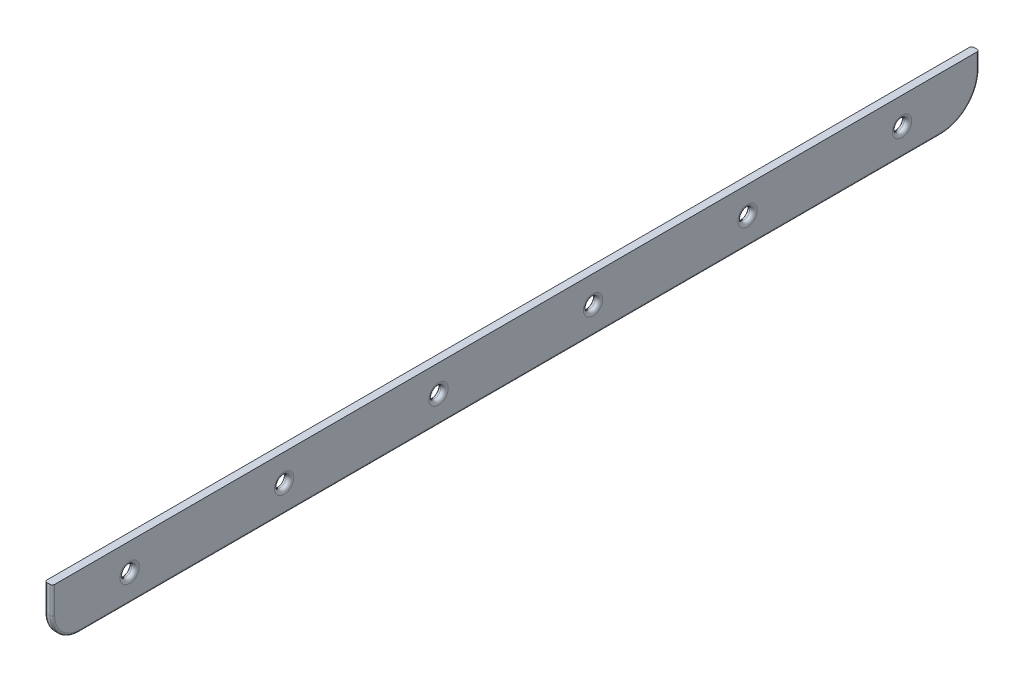
SolidWorks part; units mm, degrees
material "1.0037 (S235JR)"
ref_plane "Front Plane" through (0, 0, 0) normal (0, 0, 1) x (1, 0, 0)
ref_plane "Top Plane" through (0, 0, 0) normal (0, 1, 0) x (1, 0, 0)
ref_plane "Right Plane" through (0, 0, 0) normal (1, 0, 0) x (0, 0, -1)
sketch "Sketch1" plane through (0, 0, 0) normal (1, 0, 0) x (0, 0, -1)
  line L0 (-600, 0) -> (-600, -35)
  line L1 (-565, -70) -> (550, -70)
  line L3 (600, 0) -> (-600, 0)
  line L4 (600, -20) -> (600, 0)
  arc A0 (-600, -35) -> (-565, -70) centre (-565, -35) ccw
  arc A1 (550, -70) -> (600, -20) centre (550, -20) ccw
  circle A2 centre (-500, -35) radius 7.5
  circle A7 centre (-300, -35) radius 7.5
  circle A8 centre (-100, -35) radius 7.5
  circle A9 centre (100, -35) radius 7.5
  circle A10 centre (300, -35) radius 7.5
  circle A11 centre (500, -35) radius 7.5
  point P5 (0, 0)
  dimension "D2" = 35
  dimension "D3" = 50
  dimension "D5" = 15
  dimension "D1" = 1200
  dimension "D4" = 70
  dimension "D6" = 100
  dimension "D8" = 200
  dimension "D7" = 6
extrude "Boss-Extrude1" add sketch "Sketch1" along normal blind 10
fillet "Fillet1" radius 3 10 edges at (0, -17.5, 600) (0, -59.7487, 589.7487) (0, -10, -600) (0, -55.3553, -585.3553) (10, -17.5, 600) (10, -59.7487, 589.7487) (10, -10, -600) (10, -55.3553, -585.3553) (0, -70, 7.5) (10, -70, 7.5)
fillet "Fillet2" radius 5 12 edges at (0, -35, -507.5) (10, -35, -507.5) (0, -35, -307.5) (10, -35, -307.5) (0, -35, -107.5) (10, -35, -107.5) (0, -35, 92.5) (10, -35, 92.5) (0, -35, 292.5) (10, -35, 292.5) (0, -35, 492.5) (10, -35, 492.5)
